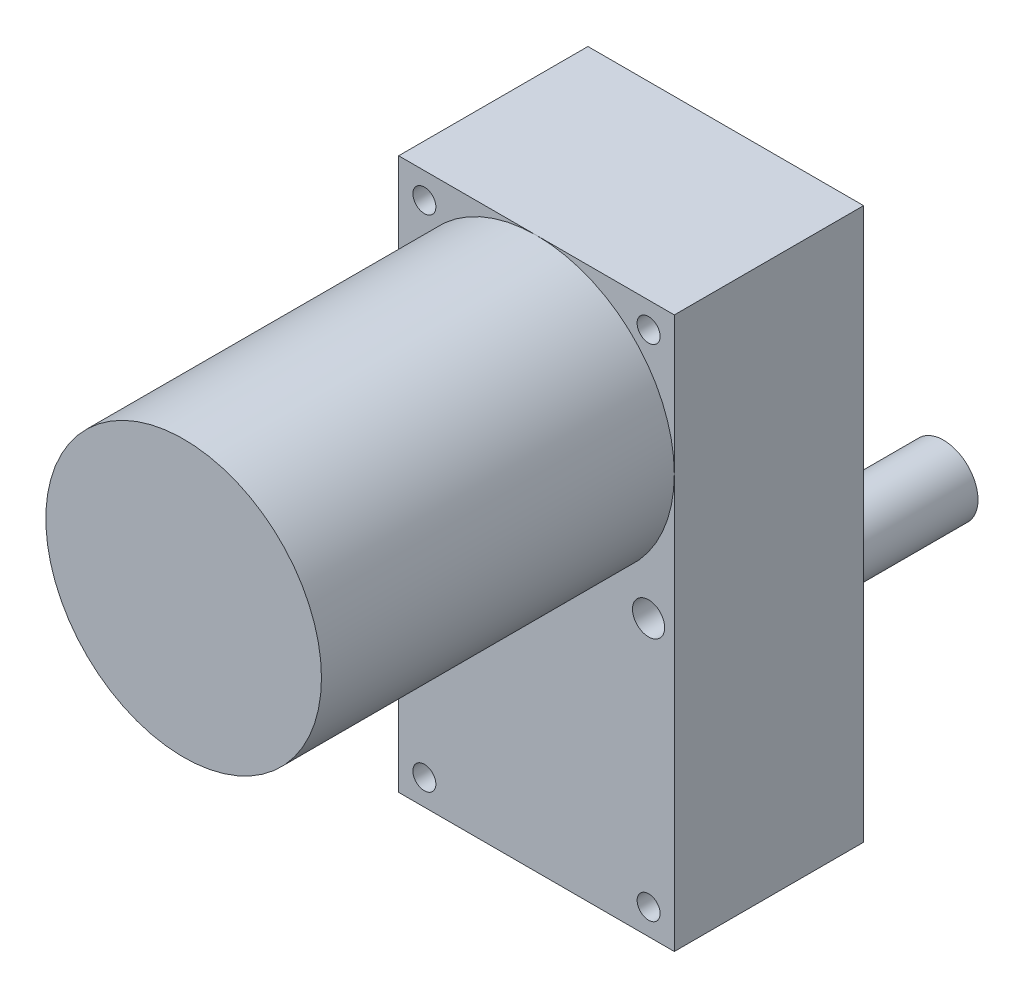
SolidWorks part; units mm, degrees
ref_plane "前视基准面" through (0, 0, 0) normal (0, 0, 1) x (1, 0, 0)
ref_plane "上视基准面" through (0, 0, 0) normal (0, 1, 0) x (1, 0, 0)
ref_plane "右视基准面" through (0, 0, 0) normal (1, 0, 0) x (0, 0, -1)
sketch "Sketch1" plane through (0, 0, 0) normal (0, 0, 1) x (1, 0, 0)
  line L0 (0, 76.2) -> (0, -14.7176) construction
  line L1 (38.1, -76.2) -> (-38.1, -76.2)
  line L2 (38.1, -76.2) -> (38.1, 76.2)
  line L3 (38.1, 76.2) -> (-38.1, 76.2)
  line L4 (-38.1, -76.2) -> (-38.1, 76.2)
  line L5 (38.1, -76.2) -> (-38.1, 76.2) construction
  line L6 (38.1, 76.2) -> (-38.1, -76.2) construction
  line L7 (38.1, 0) -> (-38.1, 0) construction
  circle A0 centre (0, 38.608) radius 23.495
  circle A1 centre (0, -38.608) radius 23.495
  circle A2 centre (-30.988, 0) radius 4.445
  circle A3 centre (30.9942, -69.088) radius 3.175
  circle A4 centre (-30.9942, -69.088) radius 3.175
  circle A5 centre (-30.988, 69.088) radius 3.175
  circle A6 centre (30.988, 0) radius 4.445
  circle A7 centre (30.988, 69.088) radius 3.175
  circle A8 centre (0, -38.608) radius 9.525
  circle A9 centre (0, -38.608) radius 3.9688
  point P0 (0, 0)
  dimension "D3" = 46.99
  dimension "D6" = 46.99
  dimension "D7" = 6.35
  dimension "D8" = 6.35
  dimension "D12" = 8.89
  dimension "D14" = 19.05
  dimension "D15" = 7.9375
  dimension "D1" = 152.4
  dimension "D2" = 76.2
  dimension "D4" = 38.608
  dimension "D5" = 38.608
  dimension "D9" = 30.988
  dimension "D10" = 69.088
  dimension "D11" = 69.088
  dimension "D13" = 30.988
extrude "Boss-Extrude1" add sketch "Sketch1" along normal blind 52.324 contours L4 L1 L2 L3 A6 A5 A4 A0 A1 A2 A3 A7 | A0 | A1 A8 | A9 | A8 A9 region at (0, 0, 0) region at (0, 38.608, 0) region at (-22.8305, -38.608, 0) region at (-9.2556, -38.608, 0) region at (0, -38.608, 0)
extrude "Boss-Extrude2" add sketch "Sketch1<3>" against normal blind 4.826 contours A0 | A1 A8 region at (0, 38.608, 0) region at (-22.8305, -38.608, 0)
sketch "Sketch1<3>" plane through (0, 0, 0) normal (0, 0, 1) x (1, 0, 0) same geometry as "Sketch1"
extrude "Boss-Extrude3" add sketch "Sketch1<5>" against normal blind 60.198 contours A8 A9 region at (-9.2556, -38.608, 0)
sketch "Sketch1<5>" plane through (0, 0, 0) normal (0, 0, 1) x (1, 0, 0) same geometry as "Sketch1"
sketch "Sketch2" plane through (0, 0, -60.198) normal (0, 0, -1) x (-1, 0, 0)
  line L0 (3.9688, -38.608) -> (9.525, -38.608) construction
  line L1 (8.9803, -35.433) -> (4.4279, -35.433)
  line L2 (4.4279, -35.433) -> (4.4279, -41.783)
  line L3 (8.9803, -41.783) -> (4.4279, -41.783)
  circle A0 centre (0, -38.608) radius 3.9688 construction
  circle A1 centre (0, -38.608) radius 9.525 construction
  arc A4 (8.9803, -35.433) -> (8.9803, -41.783) centre (0, -38.608) cw
  dimension "D1" = 3.175
extrude "Cut-Extrude1" cut sketch "Sketch2" against normal blind 26.924
sketch "Sketch4" plane through (0, 0, 52.324) normal (0, 0, 1) x (1, 0, 0)
  line L0 (38.1, 76.2) -> (-38.1, 76.2) construction
  circle A0 centre (0, 38.1) radius 38.1
  dimension "D2" = 76.2
  dimension "D1" = 38.1
extrude "Boss-Extrude4" add sketch "Sketch4" along normal blind 97.536
